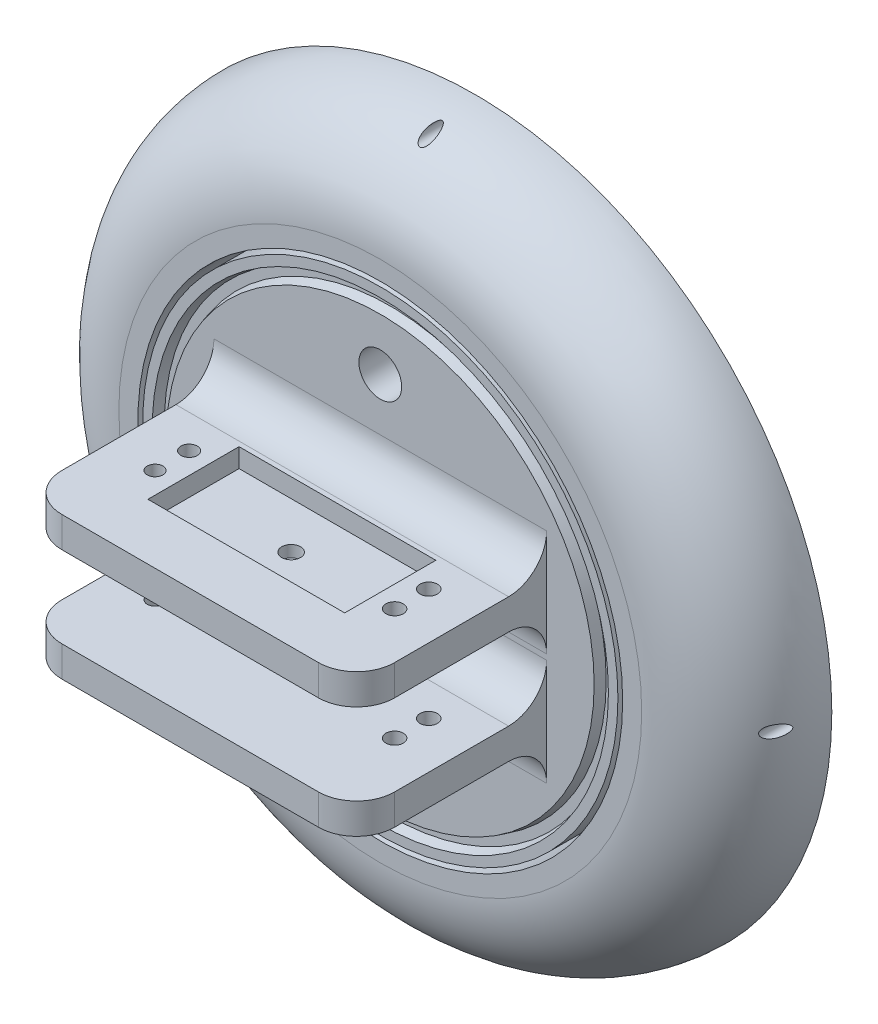
SolidWorks part; units mm, degrees
ref_plane "Front Plane" through (0, 0, 0) normal (0, 0, 1) x (1, 0, 0)
ref_plane "Top Plane" through (0, 0, 0) normal (0, 1, 0) x (1, 0, 0)
ref_plane "Right Plane" through (0, 0, 0) normal (1, 0, 0) x (0, 0, -1)
sketch "Sketch1" plane through (0, 0, 0) normal (0, 0, 1) x (1, 0, 0)
  circle A1 centre (0, 0) radius 37.5
  circle A2 centre (0, 36.25) radius 0.625
  dimension "D1" = 36.25
  dimension "D2" = 75
  dimension "D3" = 1.25
extrude "Boss-Extrude2" add sketch "Sketch1" along normal blind 10
sketch "Sketch3" plane through (0, 0, 10) normal (0, 0, 1) x (1, 0, 0)
  circle A0 centre (36.25, 0) radius 0.625
  circle A1 centre (0, -36.25) radius 0.625
  circle A2 centre (-36.25, 1.1747) radius 0.625
  dimension "D1" = 1.25
  dimension "D2" = 1.25
  dimension "D3" = 1.25
  dimension "D4" = 36.25
  dimension "D5" = 36.25
  dimension "D6" = 36.25
extrude "Cut-Extrude1" cut sketch "Sketch3" against normal through all
sketch "Sketch4" plane through (0, 0, 10) normal (0, 0, 1) x (1, 0, 0)
  circle A0 centre (0, 0) radius 24
  circle A1 centre (0, 0) radius 22.5
  circle A2 centre (-21.0235, 9.8448) radius 0.478
  circle A3 centre (-15.6557, 17.1407) radius 0.478
  circle A4 centre (-7.9045, 21.8272) radius 0.478
  circle A5 centre (1.05, 23.1906) radius 0.478
  circle A6 centre (9.8448, 21.0235) radius 0.478
  circle A7 centre (17.1407, 15.6557) radius 0.478
  circle A8 centre (21.8272, 7.9045) radius 0.478
  circle A9 centre (23.1906, -1.05) radius 0.478
  circle A10 centre (21.0235, -9.8448) radius 0.478
  circle A11 centre (15.6557, -17.1407) radius 0.478
  circle A12 centre (7.9045, -21.8272) radius 0.478
  circle A13 centre (-1.05, -23.1906) radius 0.478
  circle A14 centre (-9.8448, -21.0235) radius 0.478
  circle A15 centre (-17.1407, -15.6557) radius 0.478
  circle A16 centre (-21.8272, -7.9045) radius 0.478
  circle A17 centre (-23.1906, 1.05) radius 0.478
  dimension "D1" = 48
  dimension "45" = 45
  dimension "D2" = 16
extrude "Cut-Extrude7" cut sketch "Sketch4" against normal blind 1 draft 15 contours A0 | A1
sketch "Sketch5" plane through (0, 0, 10) normal (0, 0, 1) x (1, 0, 0)
  circle A0 centre (0, 0) radius 25
  circle A1 centre (0, 0) radius 25.5
  dimension "D1" = 50
  dimension "D2" = 51
extrude "Cut-Extrude9" cut sketch "Sketch5" against normal through all
sketch "Sketch6" plane through (0, 0, 10) normal (0, 0, 1) x (1, 0, 0)
  circle A0 centre (0, 3) radius 0.5
  circle A1 centre (3, 0) radius 0.5
  circle A2 centre (0, -2.4843) radius 0.5
  circle A3 centre (-3, 0) radius 0.5
  dimension "D1" = 1
  dimension "D6" = 1
  dimension "D7" = 1
  dimension "D8" = 1
  dimension "D2" = 3
  dimension "D3" = 3
  dimension "D4" = 3
  dimension "D5" = 2.4843
extrude "Cut-Extrude11" cut sketch "Sketch6" against normal through all
sketch "Sketch7" plane through (0, 0, 10) normal (0, 0, 1) x (1, 0, 0)
  line L1 (-17.5, -7.5) -> (17.5, -7.5)
  line L2 (-17.5, -7.5) -> (-17.5, 7.5)
  line L3 (-17.5, 7.5) -> (17.5, 7.5)
  line L4 (17.5, -7.5) -> (17.5, 7.5)
  line L5 (-17.5, -7.5) -> (17.5, 7.5) construction
  line L6 (-17.5, 7.5) -> (17.5, -7.5) construction
  point P0 (0, 0)
  dimension "D1" = 35
  dimension "D2" = 15
extrude "Boss-Extrude3" add sketch "Sketch7" along normal blind 20 contours L2 L1 L4 L3
sketch "Sketch8" plane through (0, 7.5, 0) normal (0, 1, 0) x (1, 0, 0)
  line L1 (-10.3506, -14.5053) -> (10.3506, -14.5053)
  line L2 (-10.3506, -14.5053) -> (-10.3506, -24.0949)
  line L3 (-10.3506, -24.0949) -> (10.3506, -24.0949)
  line L4 (10.3506, -14.5053) -> (10.3506, -24.0949)
  line L5 (-10.3506, -14.5053) -> (10.3506, -24.0949) construction
  line L6 (-10.3506, -24.0949) -> (10.3506, -14.5053) construction
  circle A0 centre (12.6006, -17.5053) radius 0.9133
  circle A1 centre (12.6006, -21.0949) radius 0.9133
  circle A2 centre (-12.6006, -21.0949) radius 0.8197
  circle A3 centre (-12.6006, -17.5053) radius 0.8611
  point P0 (0, -19.3001)
  dimension "D4" = 3
  dimension "D5" = 2.25
  dimension "D6" = 2.25
  dimension "D9" = 2.25
  dimension "D1" = 3
  dimension "D2" = 3
  dimension "D3" = 3
  dimension "D7" = 2.25
  dimension "D8" = 9.5896
extrude "Cut-Extrude12" cut sketch "Sketch8" against normal blind 2 contours L2 L1 L4 L3 | A0 | A1 | A2 | A3
sketch "Sketch9" plane through (0, 5.5, 0) normal (0, 1, 0) x (1, 0, 0)
  circle A0 centre (12.6006, -17.5053) radius 0.9133
  circle A1 centre (12.6006, -21.0949) radius 0.9133
  circle A2 centre (-12.6006, -21.0949) radius 0.8197
  circle A3 centre (-12.6006, -17.5053) radius 0.8611
extrude "Cut-Extrude13" cut sketch "Sketch9" against normal through all
sketch "Sketch10" plane through (0, 5.5, 0) normal (0, 1, 0) x (1, 0, 0)
  circle A0 centre (0, -19.3762) radius 0.9894
extrude "Cut-Extrude14" cut sketch "Sketch10" against normal through all
sketch "Sketch11" plane through (0, 0, 30) normal (0, 0, 1) x (1, 0, 0)
  line L0 (-17.5, -7.5) -> (-17.5, 7.5) construction
  line L1 (17.5, -4.2844) -> (-17.5, -4.2844)
  line L2 (17.5, -4.2844) -> (17.5, 4.2844)
  line L3 (17.5, 4.2844) -> (-17.5, 4.2844)
  line L4 (-17.5, -4.2844) -> (-17.5, 4.2844)
  line L5 (17.5, -4.2844) -> (-17.5, 4.2844) construction
  line L6 (17.5, 4.2844) -> (-17.5, -4.2844) construction
  point P0 (0, 0)
extrude "Cut-Extrude15" cut sketch "Sketch11" against normal up to vertex (20 mm away) up to point (-17.5, 7.5, 10)
fillet "Fillet2" radius 10 1 edges at (37.5, 0, 10)
fillet "Fillet4" radius 4 4 edges at (-17.5, -5.8922, 30) (17.5, 5.8922, 30) (17.5, -5.8922, 30) (-17.5, 5.8922, 30)
fillet "Fillet5" radius 4 4 edges at (0, 4.2844, 10) (0, -4.2844, 10) (0, -7.5, 10) (0, 7.5, 10)
sketch "Sketch12" plane through (0, 0, 10) normal (0, 0, 1) x (1, 0, 0)
  circle A0 centre (0, 17) radius 2.25
  circle A1 centre (0, -17) radius 2.25
  circle A2 centre (0, 0) radius 22.5 construction
  circle A3 centre (0, 0) radius 25 construction
  dimension "D1" = 4.5
  dimension "D2" = 4.5
  dimension "D3" = 17
  dimension "D4" = 17
extrude "Cut-Extrude16" cut sketch "Sketch12" against normal through all
sketch "Sketch13" plane through (0, 0, 0) normal (0, 0, -1) x (-1, 0, 0)
  line L1 (-15.5, -12.3608) -> (-5.5, -12.3608)
  line L2 (-15.5, -12.3608) -> (-15.5, 12.6392)
  line L3 (-15.5, 12.6392) -> (-5.5, 12.6392)
  line L4 (-5.5, -12.3608) -> (-5.5, 12.6392)
  line L5 (-15.5, -12.3608) -> (-5.5, 12.6392) construction
  line L6 (-15.5, 12.6392) -> (-5.5, -12.3608) construction
  line L7 (5.5, -12.3608) -> (15.5, -12.3608)
  line L8 (5.5, -12.3608) -> (5.5, 12.6392)
  line L9 (5.5, 12.6392) -> (15.5, 12.6392)
  line L10 (15.5, -12.3608) -> (15.5, 12.6392)
  line L11 (5.5, -12.3608) -> (15.5, 12.6392) construction
  line L12 (5.5, 12.6392) -> (15.5, -12.3608) construction
  circle A0 centre (0, 0) radius 25 construction
  point P0 (-10.5, 0.1392)
  point P5 (10.5, 0.1392)
  dimension "D5" = 15.5
  dimension "D1" = 25
  dimension "D2" = 25
  dimension "D3" = 10
  dimension "D4" = 10
  dimension "D6" = 15.5
extrude "Cut-Extrude17" cut sketch "Sketch13" against normal blind 4
